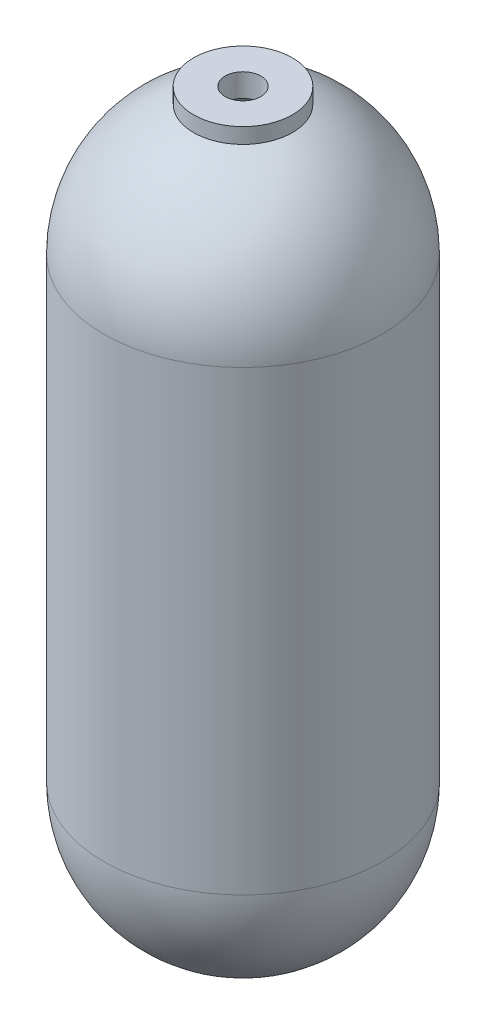
SolidWorks part; units mm, degrees
ref_plane "Front Plane" through (0, 0, 0) normal (0, 0, 1) x (1, 0, 0)
ref_plane "Top Plane" through (0, 0, 0) normal (0, 1, 0) x (1, 0, 0)
ref_plane "Right Plane" through (0, 0, 0) normal (1, 0, 0) x (0, 0, -1)
sketch "Sketch4" plane through (0, 0, 0) normal (0, 0, 1) x (1, 0, 0)
  line L0 (0, 80.4479) -> (0, -245.0345) construction
  line L1 (20.32, 59.7655) -> (20.32, 53.4155)
  line L3 (57.15, 0) -> (57.15, -187.8845)
  line L4 (50.8, 0) -> (50.8, -187.8845)
  line L5 (0, -238.6845) -> (0, -245.0345)
  line L6 (13.97, 59.7655) -> (20.32, 59.7655)
  line L7 (13.97, 59.7655) -> (2.54, 59.7655)
  line L8 (2.54, 59.7655) -> (2.54, 50.7365)
  line L9 (13.97, 59.7655) -> (13.97, 48.8414) construction
  arc A0 (57.15, -187.8845) -> (0, -245.0345) centre (0, -187.8845) cw
  arc A1 (57.15, 0) -> (20.32, 53.4155) centre (0, 0) ccw
  arc A2 (50.8, 0) -> (13.97, 48.8414) centre (0, 0) ccw
  arc A3 (50.8, -187.8845) -> (0, -238.6845) centre (0, -187.8845) cw
  arc A4 (13.97, 48.8414) -> (2.54, 50.7365) centre (0, 0) ccw
  dimension "D3" = 304.8
  dimension "D1" = 20.32
  dimension "D2" = 57.15
  dimension "D4" = 6.35
  dimension "D6" = 17.78
  dimension "D5" = 6.35
revolve "Revolve1" add sketch "Sketch4" angle 360 about L0
hole_wizard "5/8-18 Tapped Hole2" positions "Sketch8" profile "Sketch7" tap size "5/8-18" standard "ANSI Inch"
sketch "Sketch8" plane through (0, 59.7655, 0) normal (0, 1, 0) x (1, 0, 0)
  point P0 (0, 0)
sketch "Sketch7" plane through (0, 59.7655, 0) normal (1, 0, 0) x (0, 0, 1)
  line L0 (0, 0) -> (0, 43.2734)
  line L1 (0, 43.2734) -> (7.3419, 38.862)
  line L2 (7.3419, 38.862) -> (7.3419, 0)
  line L5 (7.3419, 0) -> (0, 0)
  line L10 (0, 43.2734) -> (-7.3419, 38.862) construction
  line L11 (0, -6.35) -> (0, 107.95) construction
  dimension "Tap Drill Dia." = 14.6837
  dimension "Tap Drill Depth" = 38.862
  dimension "Drill Angle" = 118
cosmetic thread "Hole Thread1" parameters "D1"=11.8044, "D2"=15.875
ref_axis "Axis1" through (0, -187.8845, 0) along (0, 1, 0)
